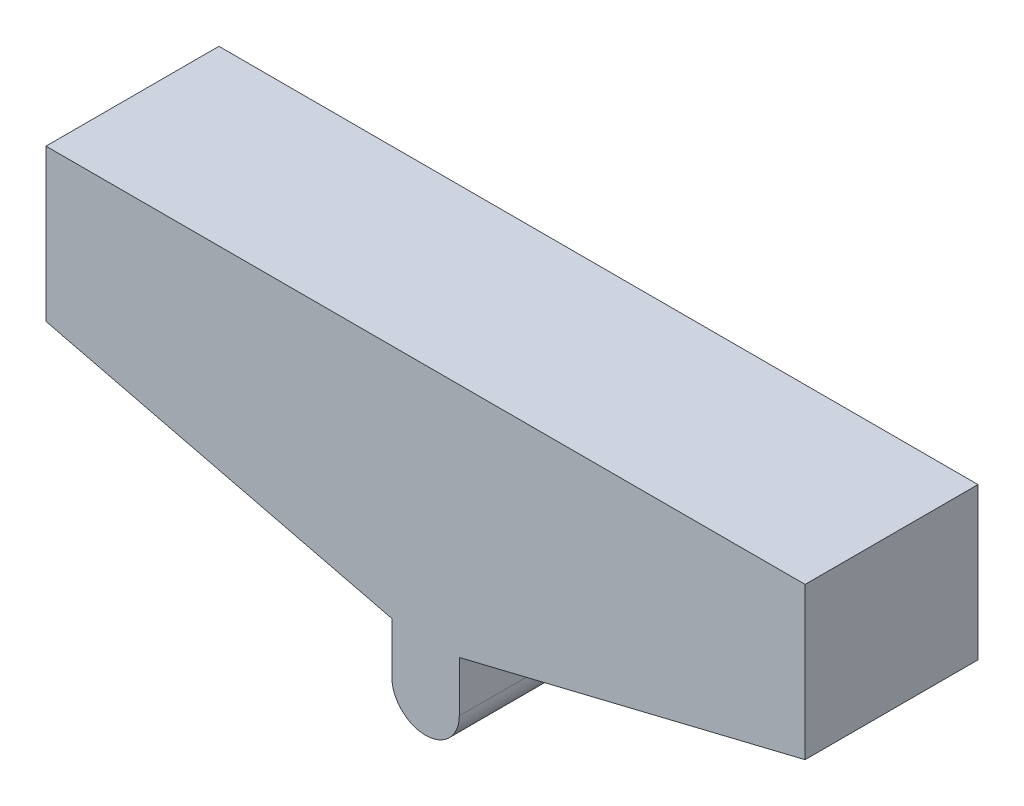
SolidWorks part; units mm, degrees
ref_plane "Front Plane" through (0, 0, 0) normal (0, 0, 1) x (1, 0, 0)
ref_plane "Top Plane" through (0, 0, 0) normal (0, 1, 0) x (1, 0, 0)
ref_plane "Right Plane" through (0, 0, 0) normal (1, 0, 0) x (0, 0, -1)
sketch "Sketch1" plane through (0, 0, 0) normal (0, 0, 1) x (1, 0, 0)
  line L0 (4, -9) -> (-4, -9)
  line L1 (-45, -9) -> (45, -9)
  line L2 (-45, -9) -> (-45, 9)
  line L3 (-45, 9) -> (45, 9)
  line L4 (45, -9) -> (45, 9)
  line L5 (-45, -9) -> (45, 9) construction
  line L6 (-45, 9) -> (45, -9) construction
  line L7 (-22.5, -3) -> (-7.5, -3)
  line L8 (-22.5, -3) -> (-22.5, 3)
  line L9 (-22.5, 3) -> (-7.5, 3)
  line L10 (-7.5, -3) -> (-7.5, 3)
  line L11 (-22.5, -3) -> (-7.5, 3) construction
  line L12 (-22.5, 3) -> (-7.5, -3) construction
  line L13 (7.5, -3) -> (22.5, -3)
  line L14 (7.5, -3) -> (7.5, 3)
  line L15 (7.5, 3) -> (22.5, 3)
  line L16 (22.5, -3) -> (22.5, 3)
  line L17 (7.5, -3) -> (22.5, 3) construction
  line L18 (7.5, 3) -> (22.5, -3) construction
  line L19 (4, -9) -> (4, -29)
  line L20 (-4, -9) -> (-4, -29)
  line L21 (4, -29) -> (-4, -29)
  line L22 (45, -9) -> (4, -19)
  line L23 (-4, -19) -> (-45, -9)
  point P0 (0, 0)
  point P6 (-15, 0)
  point P11 (15, 0)
  dimension "D1" = 90
  dimension "D2" = 18
  dimension "D3" = 6
  dimension "D4" = 6
  dimension "D5" = 6
  dimension "D6" = 6
  dimension "D7" = 15
  dimension "D8" = 15
  dimension "D9" = 7.5
  dimension "D10" = 7.5
  dimension "D11" = 8
  dimension "D12" = 4
  dimension "D13" = 20
extrude "Boss-Extrude1" add sketch "Sketch1" along normal blind 14 contours L1 L4 L3 L2 L0 L16 L13 L14 L15 L10 L7 L8 L9 | L21 L19 L0 L20 | L7 L10 L9 L8 | L13 L16 L15 L14 | L22 L1 L19 | L23 L20 L1 region at (0, -19, 0) region at (0, 0, 0) region at (17.6667, -12.3333, 0) region at (-17.6667, -12.3333, 0) region at (-15, 0, 0) region at (15, 0, 0)
sketch "Sketch3" plane through (0, 0, 0) normal (0, 0, 1) x (1, 0, 0)
  line L0 (4, -9) -> (-4, -9)
  line L1 (-45, -9) -> (45, -9)
  line L2 (-45, -9) -> (-45, 9)
  line L3 (-45, 9) -> (45, 9)
  line L4 (45, -9) -> (45, 9)
  line L5 (-45, -9) -> (45, 9) construction
  line L6 (-45, 9) -> (45, -9) construction
  line L7 (-22.5, -3) -> (-7.5, -3)
  line L8 (-22.5, -3) -> (-22.5, 3)
  line L9 (-22.5, 3) -> (-7.5, 3)
  line L10 (-7.5, -3) -> (-7.5, 3)
  line L11 (-22.5, -3) -> (-7.5, 3) construction
  line L12 (-22.5, 3) -> (-7.5, -3) construction
  line L13 (7.5, -3) -> (22.5, -3)
  line L14 (7.5, -3) -> (7.5, 3)
  line L15 (7.5, 3) -> (22.5, 3)
  line L16 (22.5, -3) -> (22.5, 3)
  line L17 (7.5, -3) -> (22.5, 3) construction
  line L18 (7.5, 3) -> (22.5, -3) construction
  line L19 (4, -9) -> (4, -29)
  line L20 (-4, -9) -> (-4, -29)
  line L21 (4, -29) -> (-4, -29)
  point P0 (0, 0)
  point P6 (-15, 0)
  point P11 (15, 0)
  dimension "D1" = 90
  dimension "D2" = 18
  dimension "D3" = 6
  dimension "D4" = 6
  dimension "D5" = 6
  dimension "D6" = 6
  dimension "D7" = 15
  dimension "D8" = 15
  dimension "D9" = 7.5
  dimension "D10" = 7.5
  dimension "D11" = 8
  dimension "D12" = 4
  dimension "D13" = 20
extrude "Boss-Extrude2" add sketch "Sketch3" against normal blind 6.5 contours L1 L4 L3 L2 L0 L16 L13 L14 L15 L10 L7 L8 L9 | L21 L19 L0 L20 region at (0, -19, 0) region at (0, 0, 0)
fillet "Fillet1" radius 4 2 edges at (-4, -29, 3.75) (4, -29, 3.75)
